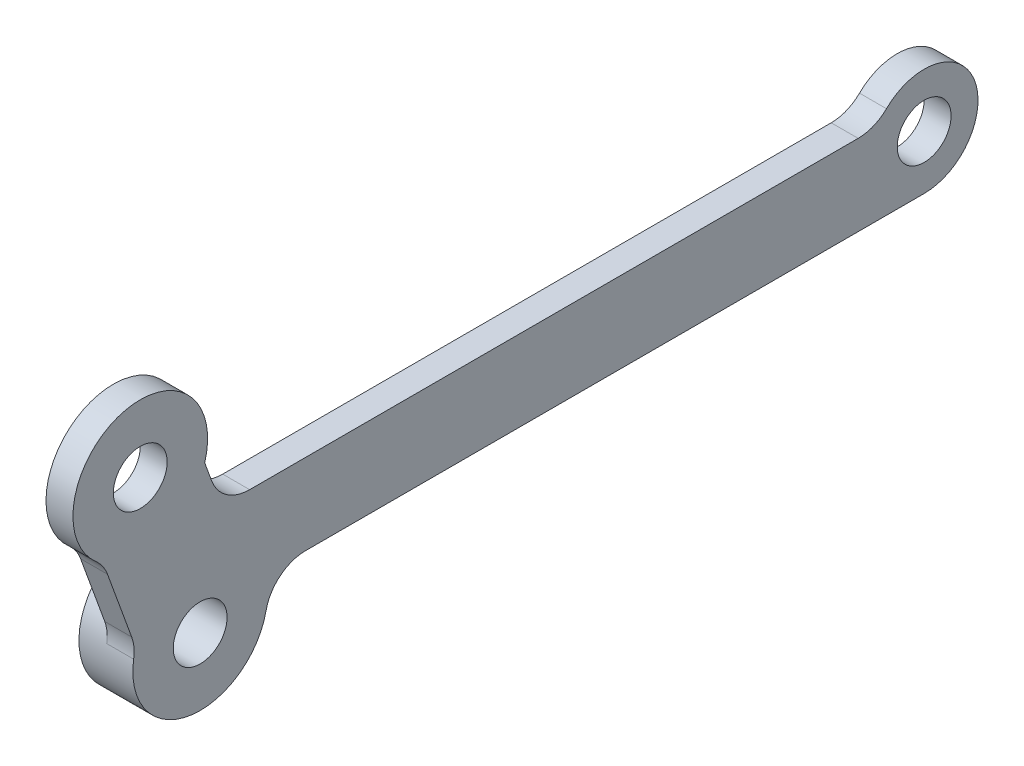
SolidWorks part; units mm, degrees
ref_plane "前视基准面" through (0, 0, 0) normal (0, 0, 1) x (1, 0, 0)
ref_plane "上视基准面" through (0, 0, 0) normal (0, 1, 0) x (1, 0, 0)
ref_plane "右视基准面" through (0, 0, 0) normal (1, 0, 0) x (0, 0, -1)
other "Configuration Table"
sketch "草图1" plane through (0, 0, 0) normal (1, 0, 0) x (0, 0, -1)
  line L1 (0, 0) -> (52.1838, 0)
  line L2 (0, 0) -> (2.1838, -6)
  line L3 (2.1838, -6) -> (52.1838, -6)
  line L4 (52.1838, 0) -> (52.1838, -6)
  line L5 (-9.78, 3.4798) -> (-2.2624, 6.216)
  line L6 (-9.78, 3.4798) -> (-5.3337, -8.7362)
  line L7 (-5.3337, -8.7362) -> (2.1838, -6)
  line L8 (-2.2624, 6.216) -> (2.1838, -6)
  circle A0 centre (-6.0212, 4.8479) radius 5
  circle A1 centre (-1.5749, -7.3681) radius 5
  circle A3 centre (52.1838, -2) radius 4
  circle A4 centre (-6.0212, 4.8479) radius 2
  circle A5 centre (52.1838, -2) radius 2
  circle A6 centre (-1.5749, -7.3681) radius 2
  dimension "D5" = 10
  dimension "D6" = 10
  dimension "D8" = 8
  dimension "D9" = 4
  dimension "D1" = 110
  dimension "D2" = 50
  dimension "D3" = 6
  dimension "D4" = 8
  dimension "D7" = 13
extrude "凸台-拉伸1" add sketch "草图1" along normal blind 2 contours A3 L1 L2 A1 L3 | A0 | L8 L5 L6 L7 | A1 | A3 region at (0, -2.9846, -25.1334)
extrude "凸台-拉伸2" add sketch "草图1<4>" against normal blind 2 contours A1
sketch "草图1<4>" plane through (0, 0, 0) normal (1, 0, 0) x (0, 0, -1) same geometry as "草图1"
extrude "切除-拉伸1" cut sketch "草图1<3>" along normal through all both and the other way through all contours A4 | A6 | A5
sketch "草图1<3>" plane through (0, 0, 0) normal (1, 0, 0) x (0, 0, -1) same geometry as "草图1"
fillet "圆角1" radius 3 5 edges at (1, 0, -48.7197) (1, -5.9171, 6.3598) (1, 0.6608, 8.7539) (1, -6, -3.2342) (1, 0, 0)
